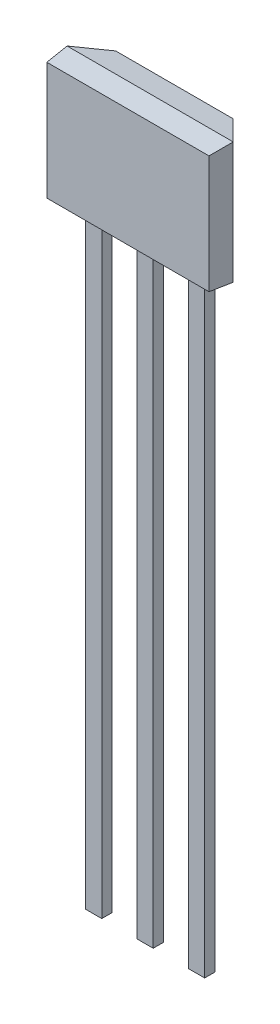
SolidWorks part; units mm, degrees
ref_plane "前基準面" through (0, 0, 0) normal (0, 0, 1) x (1, 0, 0)
ref_plane "上基準面" through (0, 0, 0) normal (0, 1, 0) x (1, 0, 0)
ref_plane "右基準面" through (0, 0, 0) normal (1, 0, 0) x (0, 0, -1)
sketch "草圖1" plane through (0, 0, 0) normal (0, 0, 1) x (1, 0, 0)
  line L1 (-2.05, 1.5) -> (2.05, 1.5)
  line L2 (-2.05, 1.5) -> (-2.05, -1.5)
  line L3 (-2.05, -1.5) -> (2.05, -1.5)
  line L4 (2.05, 1.5) -> (2.05, -1.5)
  line L5 (-2.05, 1.5) -> (2.05, -1.5) construction
  line L6 (-2.05, -1.5) -> (2.05, 1.5) construction
  point P0 (0, 0)
  dimension "D1" = 4.1
  dimension "D2" = 3
extrude "填料-伸長1" add sketch "草圖1" along normal blind 1.15
sketch "草圖2" plane through (0, -1.5, 0) normal (0, -1, 0) x (1, 0, 0)
  line L0 (-2.05, 1.15) -> (-2.05, 0.6)
  line L1 (-2.05, 1.15) -> (-2.05, 0) construction
  line L2 (-2.05, 0.6) -> (-2.0019, 1.15)
  line L3 (-2.05, 1.15) -> (2.05, 1.15) construction
  line L4 (-2.0019, 1.15) -> (-2.05, 1.15)
  line L5 (0, 0) -> (0, 1.15) construction
  line L6 (-2.05, 0.6) -> (-1.45, 0)
  line L7 (-2.05, 0) -> (2.05, 0) construction
  line L8 (-1.45, 0) -> (-2.05, 0)
  line L9 (-2.05, 0) -> (-2.05, 0.6)
  line L10 (2.05, 0) -> (2.05, 0.6)
  line L11 (1.45, 0) -> (2.05, 0)
  line L12 (2.05, 0.6) -> (1.45, 0)
  line L13 (2.0019, 1.15) -> (2.05, 1.15)
  line L14 (2.05, 0.6) -> (2.0019, 1.15)
  line L15 (2.05, 1.15) -> (2.05, 0.6)
  line M7 (-2.05, 0) -> (2.05, 0)
  line M8 (2.05, 0) -> (2.05, 1.15)
  line M10 (-2.05, 1.15) -> (-2.05, 0)
  dimension "D1" = 0.55
  dimension "D2" = 5
  dimension "D3" = 45
extrude "除料-伸長1" cut sketch "草圖2" against normal through all contours L6 M10 M7 | L12 M8 M7 | L2 L4 L0 | L14 L13 L15 region at (1.85, -1.5, 0.2) region at (-1.85, -1.5, 0.2)
ref_plane "平面1" through (2.5, 0, 0) normal (1, 0, 0) x (0, 0, -1)
sketch "草圖3" plane through (2.5, 0, 0) normal (1, 0, 0) x (0, 0, -1)
  line L0 (-1.15, -1.5) -> (-0.6, -1.5)
  line L1 (-0.6, -1.5) -> (-1.15, -1.4519)
  line L2 (-1.15, 1.5) -> (-1.15, -1.5) construction
  line L3 (-1.15, -1.4519) -> (-1.15, -1.5)
  line L4 (-0.6, -1.5) -> (0, -1.3942)
  line L5 (0, 1.5) -> (0, -1.5) construction
  line L6 (0, -1.3942) -> (0, -1.5)
  line L7 (0, -1.5) -> (-0.6, -1.5)
  line L8 (0, 0) -> (-1.15, 0) construction
  line L9 (0, 1.5) -> (-0.6, 1.5)
  line L10 (0, 1.3942) -> (0, 1.5)
  line L11 (-0.6, 1.5) -> (0, 1.3942)
  line L12 (-1.15, 1.4519) -> (-1.15, 1.5)
  line L13 (-0.6, 1.5) -> (-1.15, 1.4519)
  line L14 (-1.15, 1.5) -> (-0.6, 1.5)
  dimension "D1" = 5
  dimension "D2" = 10
extrude "除料-伸長2" cut sketch "草圖3" against normal through all contours L7 L6 L4 | L1 L3 L0 | L13 L12 L14 | L11 L10 L9 region at (2.5, -1.4647, 0.2)
ref_plane "平面2" through (0, 0, 0.6) normal (0, 0, 1) x (1, 0, 0)
sketch "草圖5" plane through (0, 0, 0.6) normal (0, 0, 1) x (1, 0, 0)
  line L0 (-1.27, -1.5) -> (-1.27, -16.5) construction
  line L1 (-2.05, -1.5) -> (2.05, -1.5) construction
  line L2 (0, -1.5) -> (0, -16.5) construction
  line L3 (1.27, -1.5) -> (1.27, -16.5) construction
  line L5 (-1.47, -1.4) -> (-1.07, -1.4)
  line L6 (-1.47, -1.4) -> (-1.47, -16.6)
  line L7 (-1.47, -16.6) -> (-1.07, -16.6)
  line L8 (-1.07, -1.4) -> (-1.07, -16.6)
  line L9 (-1.47, -1.4) -> (-1.07, -16.6) construction
  line L10 (-1.47, -16.6) -> (-1.07, -1.4) construction
  line L11 (-0.2, -1.4) -> (0.2, -1.4)
  line L12 (-0.2, -1.4) -> (-0.2, -16.6)
  line L13 (-0.2, -16.6) -> (0.2, -16.6)
  line L14 (0.2, -1.4) -> (0.2, -16.6)
  line L15 (-0.2, -1.4) -> (0.2, -16.6) construction
  line L16 (-0.2, -16.6) -> (0.2, -1.4) construction
  line L17 (1.07, -1.4) -> (1.47, -1.4)
  line L18 (1.07, -1.4) -> (1.07, -16.6)
  line L19 (1.07, -16.6) -> (1.47, -16.6)
  line L20 (1.47, -1.4) -> (1.47, -16.6)
  line L21 (1.07, -1.4) -> (1.47, -16.6) construction
  line L22 (1.07, -16.6) -> (1.47, -1.4) construction
  point P9 (0, -9)
  point P10 (-1.27, -9)
  point P19 (1.27, -9)
  dimension "D1" = 1.27
  dimension "D2" = 1.27
  dimension "D3" = 15
  dimension "D4" = 0.4
  dimension "D5" = 0.4
  dimension "D6" = 0.4
  dimension "D7" = 0.1
  dimension "D8" = 0.1
  dimension "D9" = 0.1
extrude "填料-伸長2" add sketch "草圖5" along normal blind 0.125 and the other way blind 0.125 separate body
ref_plane "平面3" through (0, 0, 0.41) normal (0, 0, 1) x (1, 0, 0)
sketch "草圖7" plane through (0, 0, 0.41) normal (0, 0, 1) x (1, 0, 0)
  line L0 (0, 0.79) -> (0, 0) construction
  circle A0 centre (0, 0.79) radius 0.15
  dimension "D2" = 0.3
  dimension "D1" = 0.79
extrude "填料-伸長3" add sketch "草圖7" along normal blind 0.1 separate body
